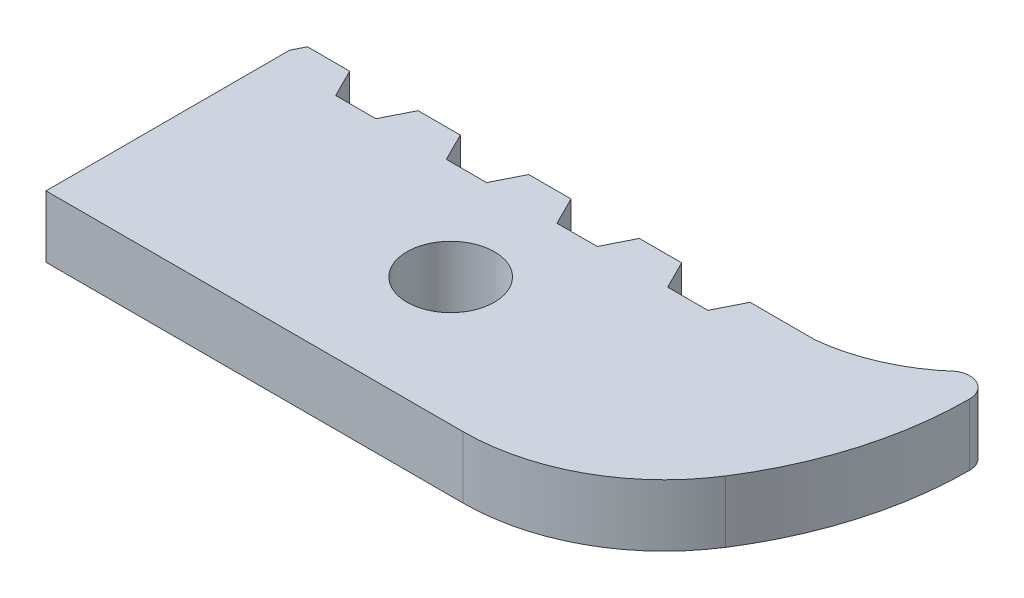
SolidWorks part; units mm, degrees
material "PET"
ref_plane "Front" through (0, 0, 0) normal (0, 0, 1) x (1, 0, 0)
ref_plane "Top" through (0, 0, 0) normal (0, 1, 0) x (1, 0, 0)
ref_plane "Right" through (0, 0, 0) normal (1, 0, 0) x (0, 0, -1)
sketch "Sketch1" plane through (0, 0, 0) normal (0, 1, 0) x (1, 0, 0)
  line L1 (-62.8447, 8.7002) -> (13.3553, 8.7002)
  line L3 (-62.8447, -3.9998) -> (13.3553, -3.9998)
  line L5 (-62.8447, 8.7002) -> (13.3553, -3.9998) construction
  line L6 (-62.8447, -3.9998) -> (13.3553, 8.7002) construction
  arc A0 (-62.8447, 8.7002) -> (-62.8447, -3.9998) centre (-62.8447, 2.3502) ccw
  arc A2 (13.3553, 8.7002) -> (13.3553, -3.9998) centre (13.3553, 2.3502) cw
  point P4 (-24.7447, 2.3502)
  dimension "D1" = 76.2
  dimension "D2" = 12.7
extrude "Boss-Extrude1" add sketch "Sketch1" along normal blind 3.075
sketch "Sketch2" plane through (0, 3.075, 0) normal (0, 1, 0) x (1, 0, 0)
  circle A0 centre (-62.8447, 2.3502) radius 2.175
  circle A1 centre (-31.0947, 2.3502) radius 2.175
  circle A2 centre (1.5553, 2.3502) radius 2.175
  arc A3 (13.3553, -3.9998) -> (13.3553, 8.7002) centre (13.3553, 2.3502) ccw construction
  dimension "D1" = 31.75
  dimension "D2" = 4.35
  dimension "D3" = 4.35
  dimension "D4" = 4.35
  dimension "D5" = 11.8
extrude "Cut-Extrude2" cut sketch "Sketch2" against normal blind 6.35 contours A1 | A0 | A2
sketch "Sketch3" plane through (0, 3.075, 0) normal (0, 1, 0) x (1, 0, 0)
  line L2 (13.3553, 8.7002) -> (13.3553, 2.3502)
  line L7 (19.7053, 2.3502) -> (19.7053, 9.9994)
  line L8 (19.7053, 2.3502) -> (13.3553, 2.3502)
  arc A0 (13.3553, -3.9998) -> (13.3553, 8.7002) centre (13.3553, 2.3502) ccw construction
  arc A2 (19.7053, 9.9994) -> (18.1741, 10.8466) centre (18.7053, 9.9994) ccw
  arc A3 (18.1741, 10.8466) -> (13.3553, 8.7002) centre (12.37, 17.3945) cw
  point P4 (25.0274, 5.3951)
  dimension "D1" = 1
  dimension "D2" = 7.6492
  dimension "D3" = 6.35
  dimension "D5" = 1.75
  dimension "D6" = 8.75
  dimension "D4" = 6.35
extrude "Boss-Extrude2" add sketch "Sketch3" against normal up to vertex (3.075 mm away) up to point (13.3553, 0, -8.7002)
sketch "Sketch4" plane through (0, 3.075, 0) normal (0, 1, 0) x (1, 0, 0)
  line L1 (19.7053, 9.9994) -> (19.7053, -6.0006)
  line L2 (19.7053, -6.0006) -> (9.2053, -6.0006)
  arc A3 (19.7053, 9.9994) -> (9.2053, -6.0006) centre (2.2054, 10.0384) cw
  arc A4 (19.7053, 9.9994) -> (18.1741, 10.8466) centre (18.7053, 9.9994) ccw construction
  dimension "D1" = 16
  dimension "D3" = 17.5
  dimension "D2" = 10.5
extrude "Cut-Extrude3" cut sketch "Sketch4" against normal blind 10
fillet "Fillet1" radius 10 1 edges at (12.6542, 1.5375, 3.9998)
sketch "Sketch5" plane through (0, 3.075, 0) normal (0, 1, 0) x (1, 0, 0)
  line L0 (-4.3147, 8.7002) -> (-0.9147, 8.7002)
  line L1 (13.3553, 8.7002) -> (-62.8447, 8.7002) construction
  line L3 (-9.8147, 8.7002) -> (-9.1147, 7.306)
  line L4 (-9.1147, 7.306) -> (-7.1147, 7.306)
  line L5 (-7.1147, 7.306) -> (-6.4147, 8.7002)
  line L14 (-4.3147, 8.7002) -> (-3.6147, 7.306)
  line L18 (-9.8147, 8.7002) -> (-6.4147, 8.7002)
  line L19 (-3.6147, 7.306) -> (-1.6147, 7.306)
  line L20 (-1.6147, 7.306) -> (-0.9147, 8.7002)
  line L21 (1.1853, 8.7002) -> (4.5853, 8.7002)
  line L22 (1.1853, 8.7002) -> (1.8853, 7.306)
  line L23 (1.8853, 7.306) -> (3.8853, 7.306)
  line L24 (3.8853, 7.306) -> (4.5853, 8.7002)
  line L25 (6.6853, 8.7002) -> (10.0853, 8.7002)
  line L26 (6.6853, 8.7002) -> (7.3853, 7.306)
  line L27 (7.3853, 7.306) -> (9.3853, 7.306)
  line L28 (9.3853, 7.306) -> (10.0853, 8.7002)
  line L29 (-15.3147, 8.7002) -> (-11.9147, 8.7002)
  line L30 (-15.3147, 8.7002) -> (-14.6147, 7.306)
  line L31 (-14.6147, 7.306) -> (-12.6147, 7.306)
  line L32 (-12.6147, 7.306) -> (-11.9147, 8.7002)
  line L33 (-20.8147, 8.7002) -> (-17.4147, 8.7002)
  line L34 (-20.8147, 8.7002) -> (-20.1147, 7.306)
  line L35 (-20.1147, 7.306) -> (-18.1147, 7.306)
  line L36 (-18.1147, 7.306) -> (-17.4147, 8.7002)
  line L37 (-26.3147, 8.7002) -> (-22.9147, 8.7002)
  line L38 (-26.3147, 8.7002) -> (-25.6147, 7.306)
  line L39 (-25.6147, 7.306) -> (-23.6147, 7.306)
  line L40 (-23.6147, 7.306) -> (-22.9147, 8.7002)
  dimension "D1" = 4
  dimension "D2" = 4
  dimension "D3" = 2
  dimension "D4" = 1.56
  dimension "D5" = 1.56
extrude "Cut-Extrude4" cut sketch "Sketch5" against normal blind 10
sketch "Sketch6" plane through (0, 3.075, 0) normal (0, 1, 0) x (1, 0, 0)
  line L0 (-62.8447, -3.9998) -> (8.5254, -3.9998) construction
  line L1 (-69.1947, 15.0502) -> (-12.2095, 15.0502)
  line L2 (-69.1947, 15.0502) -> (-69.1947, -10.3498)
  line L3 (-69.1947, -10.3498) -> (-12.2095, -10.3498)
  line L4 (-12.2095, 15.0502) -> (-12.2095, -10.3498)
  arc A1 (-62.8447, 8.7002) -> (-62.8447, -3.9998) centre (-62.8447, 2.3502) ccw construction
  dimension "D4" = 6.35
  dimension "D1" = 25.4
  dimension "D2" = 56.9852
  dimension "D3" = 6.35
extrude "Cut-Extrude5" cut sketch "Sketch6" against normal through all
